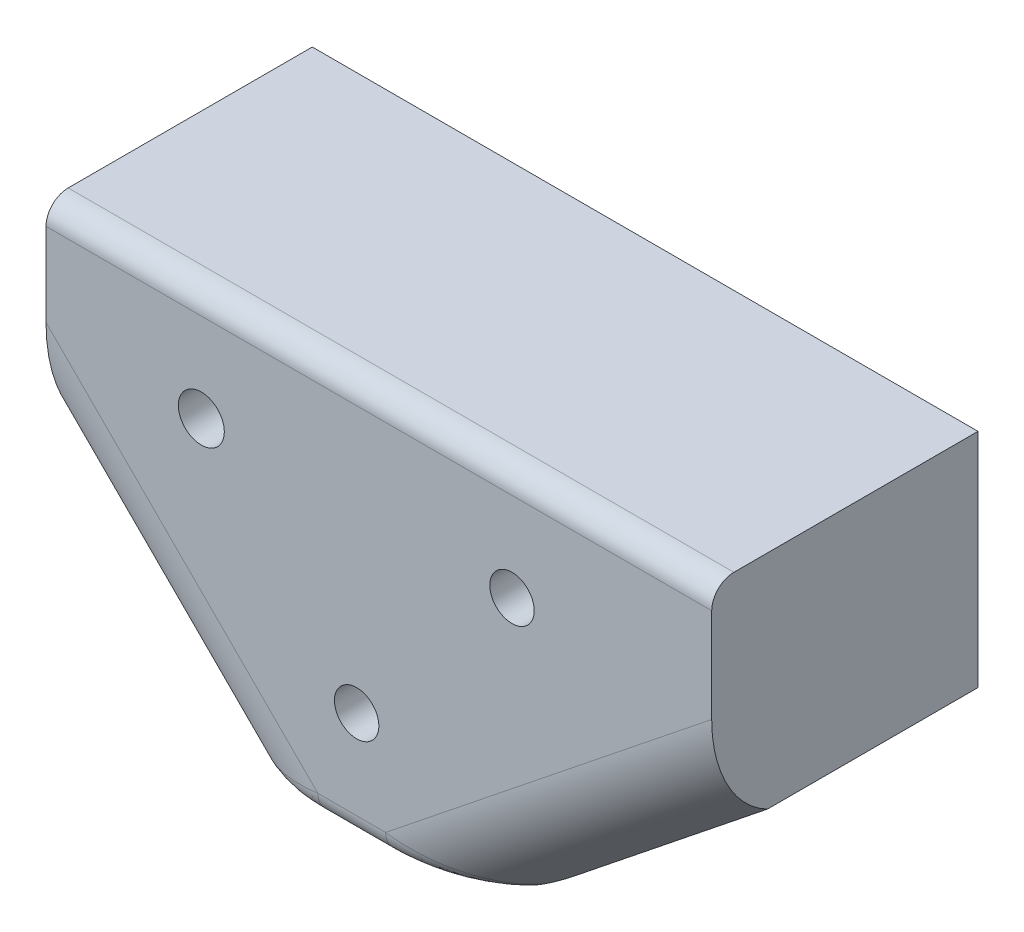
SolidWorks part; units mm, degrees
ref_plane "Plan de face" through (0, 0, 0) normal (0, 0, 1) x (1, 0, 0)
ref_plane "Plan de dessus" through (0, 0, 0) normal (0, 1, 0) x (1, 0, 0)
ref_plane "Plan de droite" through (0, 0, 0) normal (1, 0, 0) x (0, 0, -1)
sketch "Esquisse3" plane through (0, 0, 0) normal (0, 0, 1) x (1, 0, 0)
  line L0 (14, -3) -> (14, -8) construction
  line L2 (0, 0) -> (0, 10)
  line L3 (0, 10) -> (30, 10)
  line L4 (30, 0) -> (30, 10)
  line L9 (14, -8) -> (20, -8) construction
  line L10 (8, -8) -> (20, -8)
  line L12 (8, -8) -> (0, 0)
  line L13 (20, -8) -> (30, 0)
  circle A0 centre (7, 5) radius 1.036
  circle A1 centre (21, 5) radius 1
  circle A2 centre (14, -3) radius 1
  point P5 (8, -8)
  dimension "D6" = 2
  dimension "D9" = 2
  dimension "D1" = 30
  dimension "D2" = 10
  dimension "D4" = 7
  dimension "D5" = 14
  dimension "D7" = 6
extrude "Boss.-Extru.1" add sketch "Esquisse3" along normal blind 12 contours L4 L3 L2 A1 A0 region at (14.8675, 1.9655, 0)
sketch "Esquisse5" plane through (0, 0, 0) normal (1, 0, 0) x (0, 0, -1)
  line L0 (0, 0) -> (-8.1385, 0)
  line L1 (0, -8) -> (0, 0) construction
  line L2 (-8.1385, 0) -> (-9.4871, -0.7126)
  line L3 (-9.4871, -0.7126) -> (-9.4871, -8)
  line L4 (-12, 0) -> (0, 0) construction
  line L5 (-12, -8) -> (0, -8) construction
  point P4 (0, 0)
  point P5 (0, 0)
  point P12 (0, 0)
  point P13 (-10.2658, -0.8719)
  point P14 (-9.4871, -0.7126)
  dimension "D1" = 8.1385
extrude "Enlèv. mat.-Extru.2" cut sketch "Esquisse5" against normal through all and the other way through all
fillet "Congé10" radius 4 1 edges at (14.9109, -0.7126, 9.4871)
fillet "Congé11" radius 4 2 edges at (4, -4, 12) (25, -4, 12)
fillet "Congé13" radius 1 4 edges at (14, -8, 9.4871) (17.6445, -8, 11.3127) (13.6536, -8, 12) (10.081, -8, 11.3127)
fillet "Congé14" radius 1 1 edges at (15, 10, 12)
